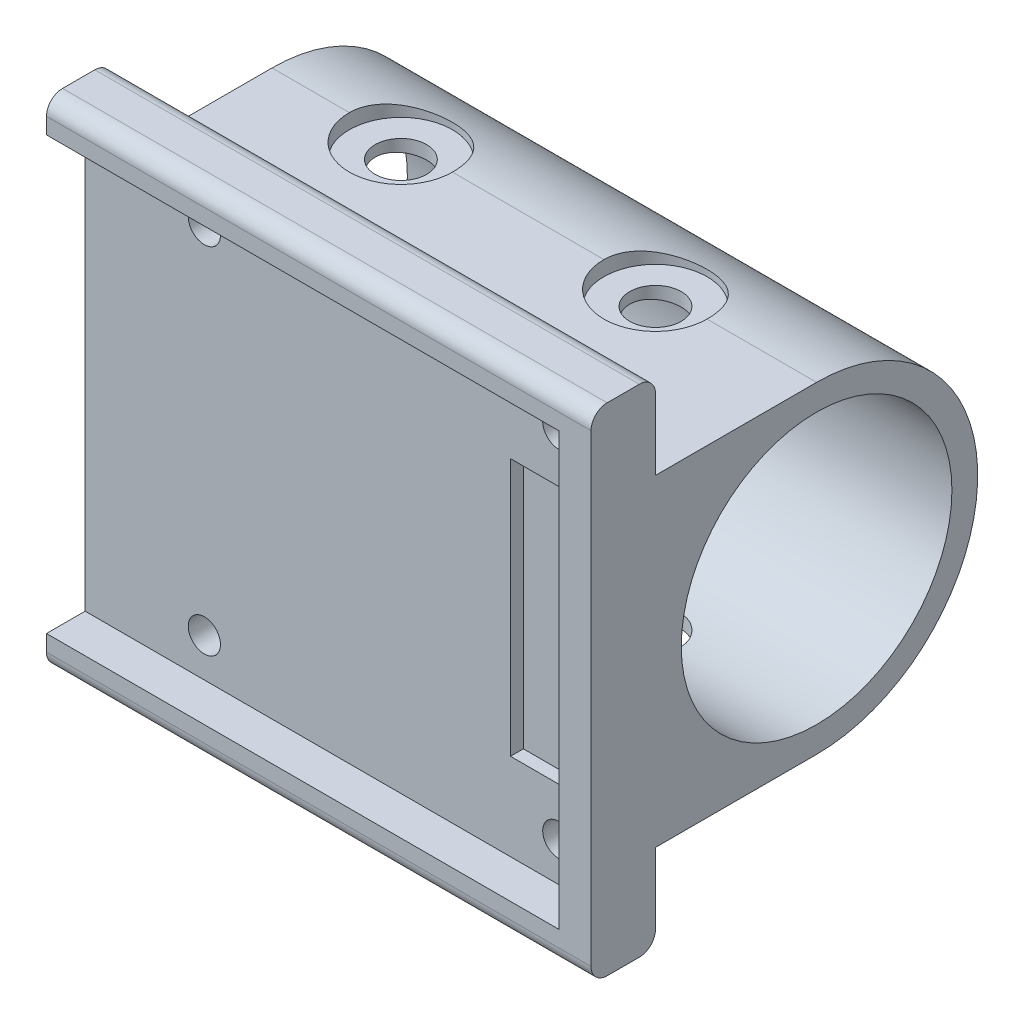
SolidWorks part; units mm, degrees
note: The reader was unsure of these and kept them because the rebuilt part matched: shared geometry of "Эскиз1<3>", "Эскиз1<5>".
ref_plane "Front Plane" through (0, 0, 0) normal (0, 0, 1) x (1, 0, 0)
ref_plane "Top Plane" through (0, 0, 0) normal (0, 1, 0) x (1, 0, 0)
ref_plane "Right Plane" through (0, 0, 0) normal (1, 0, 0) x (0, 0, -1)
sketch "Эскиз1" plane through (0, 0, 0) normal (0, 0, 1) x (1, 0, 0)
  line L0 (-17.9, -15.4) -> (-17.9, 15.4)
  line L1 (-15.9, -13.4) -> (15.9, -13.4)
  line L2 (-15.9, -13.4) -> (-15.9, 13.4)
  line L3 (-15.9, 13.4) -> (15.9, 13.4)
  line L4 (15.9, -13.4) -> (15.9, 13.4)
  line L5 (-15.9, -13.4) -> (15.9, 13.4) construction
  line L6 (-15.9, 13.4) -> (15.9, -13.4) construction
  line L7 (-17.9, 15.4) -> (17.9, 15.4)
  line L8 (17.9, -15.4) -> (17.9, 15.4)
  line L9 (-17.9, -15.4) -> (17.9, -15.4)
  line L10 (-10.1689, 0) -> (29.7254, 0) construction
  line L11 (0, 4.7614) -> (0, -7.7872) construction
  line L12 (-8.5, 11) -> (19.3163, 11) construction
  line L13 (-15.9, -13.4) -> (-15.9, -15.4)
  line L14 (-15.9, 13.4) -> (-15.9, 15.4)
  circle A0 centre (-8.5, 11) radius 1
  circle A1 centre (-8.5, -11) radius 1
  circle A2 centre (13.5, 11) radius 1
  circle A3 centre (13.5, -11) radius 1
  point P0 (0, 0)
  dimension "D4" = 2
  dimension "D8" = 22
  dimension "D1" = 26.8
  dimension "D2" = 31.8
  dimension "D5" = 2.4
  dimension "D6" = 2.4
  dimension "D7" = 22
  dimension "D3" = 2
extrude "Бобышка-Вытянуть1" add sketch "Эскиз1" along normal blind 1.6 contours L1 L4 L3 L2 A1 A0 A2 A3 | A0 | A2 | A1 | A3
extrude "Бобышка-Вытянуть2" add sketch "Эскиз1<3>" along normal blind 4
sketch "Эскиз1<3>" plane through (0, 0, 0) normal (0, 0, 1) x (1, 0, 0) same geometry as "Эскиз1"
sketch "Эскиз2" plane through (0, 0, 1.6) normal (0, 0, 1) x (1, 0, 0)
  line L1 (10.5, -8) -> (15.9, -8)
  line L2 (10.5, -8) -> (10.5, 8)
  line L3 (10.5, 8) -> (15.9, 8)
  line L4 (15.9, -8) -> (15.9, 8)
  line L5 (10.5, -8) -> (15.9, 8) construction
  line L6 (10.5, 8) -> (15.9, -8) construction
  line L7 (-15.9, 13.4) -> (15.9, 13.4) construction
  line L8 (15.9, -13.4) -> (15.9, 13.4) construction
  point P0 (13.2, 0)
  dimension "D1" = 5.4
  dimension "D3" = 5.4
extrude "Вырез-Вытянуть1" cut sketch "Эскиз2" against normal blind 0.8
sketch "Эскиз3" plane through (-15.9, 0, 0) normal (-1, 0, 0) x (0, 0, 1)
  line L0 (12.3689, 0) -> (-25.9659, 0) construction
  line L1 (0, -15.4) -> (0, 15.4) construction
  line L2 (0, 10) -> (-10, 10)
  line L3 (0, -10) -> (-10, -10)
  circle A0 centre (-10, 0) radius 10
  circle A1 centre (-10, 0) radius 8.4
  dimension "D1" = 20
  dimension "D3" = 16.8
  dimension "D2" = 1.6
extrude "Бобышка-Вытянуть3" add sketch "Эскиз3" against normal up to surface (33.8 mm away)
sketch "Эскиз4" plane through (0, 0, 0) normal (0, 1, 0) x (1, 0, 0)
  line L0 (-22.9889, 10) -> (31.9376, 10) construction
  line L1 (-15.9, 18.4) -> (-15.9, 1.6) construction
  line L2 (-15.9, 18.4) -> (-15.9, 1.6)
  line L3 (0, 29.0269) -> (0, -13.4442) construction
  circle A0 centre (-7.9, 10) radius 1.6
  circle A2 centre (7.9, 10) radius 1.6
  circle A3 centre (-7.9, 10) radius 3.2
  circle A4 centre (7.9, 10) radius 3.2
  point P8 (-15.9, 10)
  dimension "D1" = 3.2
  dimension "D3" = 6.4
  dimension "D2" = 8
extrude "Вырез-Вытянуть2" cut sketch "Эскиз4" against normal through all both and the other way through all contours A0 | A2
sketch "Эскиз5" plane through (-15.9, 0, 0) normal (-1, 0, 0) x (0, 0, 1)
  line L0 (-10, -10) -> (-10, 10) construction
  line L1 (0, 10) -> (-10, 10) construction
  line L3 (-8.4, 10) -> (-10, 10) construction
  line L4 (-8.4, 10) -> (-10, 10)
  line L5 (0, -10) -> (-10, -10) construction
  circle A0 centre (-10, 0) radius 8.4 construction
  circle A1 centre (-10, 0) radius 8.4 construction
  dimension "D1" = 10
  dimension "D2" = 10
ref_plane "Плоскость1" through (0, 10.08, 0) normal (0, 1, 0) x (1, 0, 0)
sketch "Эскиз6" plane through (0, 10.08, 0) normal (0, 1, 0) x (1, 0, 0)
  circle A1 centre (7.9, 10) radius 3.2
  circle A2 centre (7.9, 10) radius 3.2
  circle A3 centre (-7.9, 10) radius 3.2
  circle A4 centre (-7.9, 10) radius 3.2
  circle A5 centre (7.9, 10) radius 1.6
  circle A6 centre (7.9, 10) radius 1.6
  circle A7 centre (-7.9, 10) radius 1.6
  circle A8 centre (-7.9, 10) radius 1.6
  dimension "D1" = 0
  dimension "D2" = 0
  dimension "D3" = 0
  dimension "D4" = 0
extrude "Вырез-Вытянуть3" cut sketch "Эскиз6" against normal blind 1 and the other way blind 2
mirror "Зеркальное отражение1" about plane through (0, 0, 0) normal (0, 1, 0) of "Вырез-Вытянуть3"
extrude "Вырез-Вытянуть5" cut sketch "Эскиз1<5>" against normal through all from surface at 1.6 contours A2 | A0 | A1 | A3 starting at face at (6.6, 0, 1.6)
sketch "Эскиз1<5>" plane through (0, 0, 0) normal (0, 0, 1) x (1, 0, 0) same geometry as "Эскиз1"
fillet "Скругление1" radius 1 4 edges at (1, -15.4, 0) (1, -15.4, 4) (1, 15.4, 0) (1, 15.4, 4)
sketch "Эскиз7" plane through (0, 0, 0) normal (0, 0, -1) x (-1, 0, 0)
  circle A0 centre (-13.5, 11) radius 1 construction
  circle A1 centre (-13.5, -11) radius 1 construction
  circle A2 centre (8.5, -11) radius 1 construction
  circle A3 centre (8.5, 11) radius 1 construction
  circle A4 centre (-13.5, 11) radius 1
  circle A5 centre (-13.5, -11) radius 1
  circle A6 centre (8.5, -11) radius 1
  circle A7 centre (8.5, 11) radius 1
  circle A8 centre (8.5, 11) radius 1.5
  circle A9 centre (-13.5, 11) radius 1.5
  circle A10 centre (8.5, -11) radius 1.5
  circle A11 centre (-13.5, -11) radius 1.5
  dimension "D1" = 0.5
extrude "Вырез-Вытянуть6" cut sketch "Эскиз7" along normal blind 0.8
